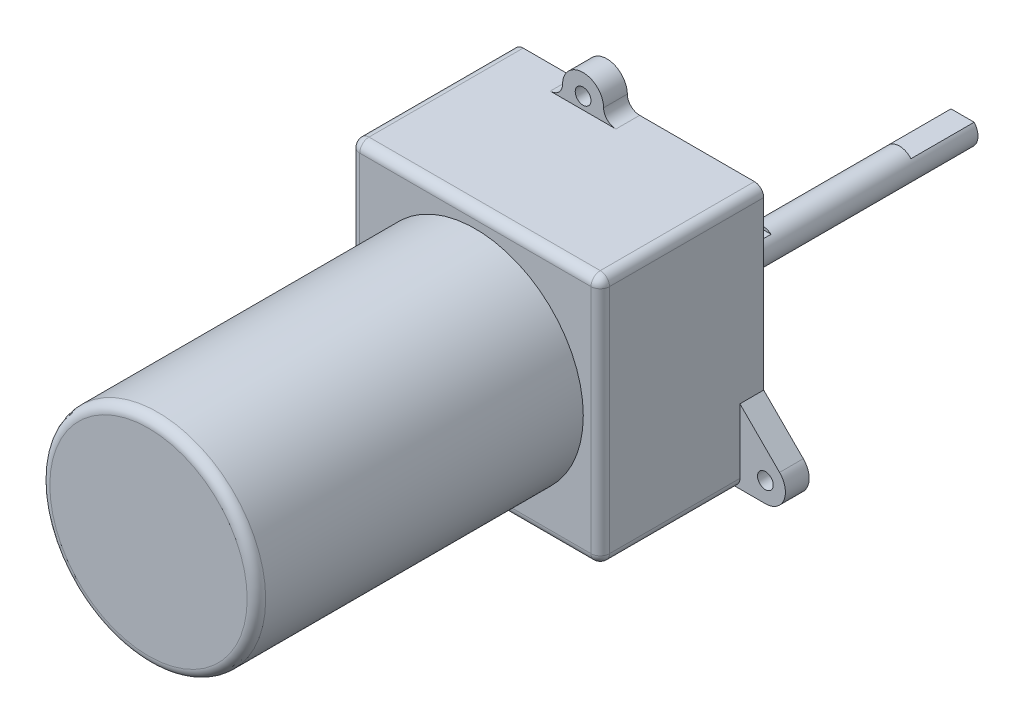
SolidWorks part; units mm, degrees
ref_plane "Front Plane" through (0, 0, 0) normal (0, 0, 1) x (1, 0, 0)
ref_plane "Top Plane" through (0, 0, 0) normal (0, 1, 0) x (1, 0, 0)
ref_plane "Right Plane" through (0, 0, 0) normal (1, 0, 0) x (0, 0, -1)
sketch "Sketch1" plane through (0, 0, 0) normal (0, 0, 1) x (1, 0, 0)
  line L0 (40.5, 0) -> (-40.5, 0) construction
  line L1 (-40.5, 56) -> (40.5, 56)
  line L2 (-40.5, 56) -> (-40.5, -25)
  line L3 (-40.5, -25) -> (40.5, -25)
  line L4 (40.5, 56) -> (40.5, -25)
  point P4 (0, 0)
  point P8 (0, 0)
  dimension "D1" = 81
  dimension "D2" = 25
extrude "Boss-Extrude1" add sketch "Sketch1" along normal blind 53
sketch "Sketch2" plane through (0, 0, 53) normal (0, 0, 1) x (1, 0, 0)
  line L0 (0, 56) -> (0, -25) construction
  line L1 (40.5, 56) -> (-40.5, 56) construction
  line L2 (-40.5, -25) -> (40.5, -25) construction
  circle A0 centre (0, 15.5) radius 35
  dimension "D1" = 70
extrude "Boss-Extrude2" add sketch "Sketch2" along normal blind 106
sketch "Sketch3" plane through (0, 0, 0) normal (0, 0, 1) x (1, 0, 0)
  circle A0 centre (0, 0) radius 5
extrude "Boss-Extrude3" add sketch "Sketch3" against normal blind 105
sketch "Sketch4" plane through (0, 0, 0) normal (0, 0, 1) x (1, 0, 0)
  line L0 (48.75, -18.5) -> (-48.75, -18.5) construction
  line L1 (-48.75, -18.5) -> (-10.369, 59.9104) construction
  line L2 (-10.369, 59.9104) -> (48.75, -18.5) construction
  line L3 (0, -44.55) -> (0, 44.55) construction
  line L5 (-40.5, -25) -> (40.5, -25) construction
  line L6 (-48.75, -25) -> (48.75, -25)
  line L7 (-53.3462, -13.9038) -> (-40.5, -1.0576)
  line L8 (-40.5, 56) -> (-40.5, -25) construction
  line L9 (-40.5, -1.0576) -> (-40.5, 56)
  line L10 (-40.5, 56) -> (-17.019, 56)
  line L11 (40.5, 56) -> (-40.5, 56) construction
  line L12 (-3.719, 59.9104) -> (-17.019, 59.9104) construction
  line L13 (-17.019, 56) -> (-17.019, 59.9104)
  line L14 (-3.719, 59.9104) -> (-3.719, 56)
  line L15 (-3.719, 56) -> (40.5, 56)
  line L16 (40.5, 56) -> (40.5, -1.0576)
  line L17 (40.5, -25) -> (40.5, 56) construction
  line L18 (40.5, -1.0576) -> (53.3462, -13.9038)
  circle A0 centre (-48.75, -18.5) radius 2.55
  circle A1 centre (48.75, -18.5) radius 2.55
  circle A2 centre (-10.369, 59.9104) radius 2.55
  arc A3 (-48.75, -25) -> (-53.3462, -13.9038) centre (-48.75, -18.5) cw
  arc A4 (48.75, -25) -> (53.3462, -13.9038) centre (48.75, -18.5) ccw
  arc A5 (-3.719, 59.9104) -> (-17.019, 59.9104) centre (-10.369, 59.9104) ccw
  point P0 (-10.369, 59.9104)
  point P1 (-48.75, -18.5)
  point P2 (48.75, -18.5)
  point P5 (0, -18.5)
  dimension "D5" = 5.1
  dimension "D1" = 97.5
  dimension "D2" = 87.3
  dimension "D3" = 98.2
  dimension "D4" = 6.5
  dimension "D6" = 13.3
  dimension "D7" = 45
  dimension "D8" = 45
extrude "Boss-Extrude4" add sketch "Sketch4" along normal blind 7.7
fillet "Fillet1" radius 4 2 edges at (-17.019, 56, 3.85) (-3.719, 56, 3.85)
fillet "Fillet2" radius 3 9 edges at (0, 56, 53) (40.5, 15.5, 53) (0, -25, 53) (-40.5, 15.5, 53) (35, 15.5, 159) (40.5, -25, 30.35) (-40.5, -25, 30.35) (-40.5, 56, 26.5) (40.5, 56, 26.5)
sketch "Sketch5" plane through (0, 0, 0) normal (0, 0, 1) x (1, 0, 0)
  line L1 (9.6488, 11.3311) -> (-9.0418, 11.3311)
  line L2 (9.6488, 11.3311) -> (9.6488, 3.3)
  line L3 (9.6488, 3.3) -> (-9.0418, 3.3)
  line L4 (-9.0418, 11.3311) -> (-9.0418, 3.3)
  circle A0 centre (0, 0) radius 5 construction
  dimension "D1" = 3.3
extrude "Cut-Extrude1" cut sketch "Sketch5" against normal blind 30 from offset 84.5 offset against normal yes
sketch "Sketch6" plane through (0, 0, 0) normal (0, 0, 1) x (1, 0, 0)
  line L0 (8.2408, 7.651) -> (8.2408, 4)
  line L1 (8.2408, 4) -> (-4, 4)
  line L2 (-4, 4) -> (-4, -6.0442)
  line L3 (-4, -6.0442) -> (-7.3935, -6.0442)
  line L4 (-7.3935, -6.0442) -> (-7.3935, 7.651)
  line L5 (-7.3935, 7.651) -> (8.2408, 7.651)
  dimension "D1" = 4
  dimension "D2" = 4
extrude "Cut-Extrude2" cut sketch "Sketch6" against normal blind 7.2 from offset 32.7 offset against normal yes
